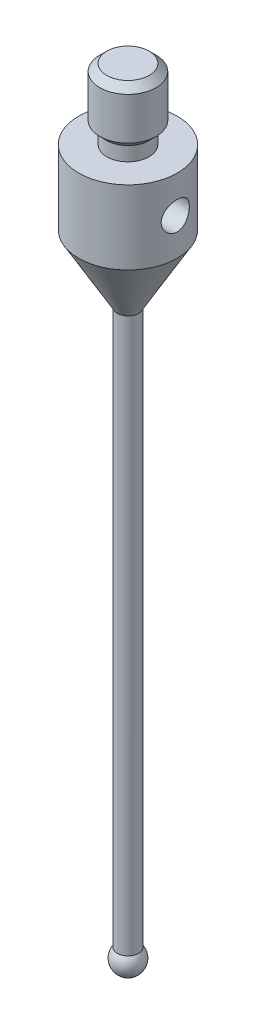
SolidWorks part; units mm, degrees
ref_plane "Front Plane" through (0, 0, 0) normal (0, 0, 1) x (1, 0, 0)
ref_plane "Top Plane" through (0, 0, 0) normal (0, 1, 0) x (1, 0, 0)
ref_plane "Right Plane" through (0, 0, 0) normal (1, 0, 0) x (0, 0, -1)
sketch "Sketch1" plane through (0, 0, 0) normal (0, 0, 1) x (1, 0, 0)
  line L0 (0, 0) -> (0, -1)
  line L1 (0, 0) -> (0, 1)
  arc A0 (0, 1) -> (0, -1) centre (0, 0) cw
  point P5 (0, -0.8177)
  dimension "D1" = 2
revolve "Revolve1" add sketch "Sketch1" angle 360 about L1 other way angle 360
sketch "Sketch2" plane through (0, 0, 0) normal (0, 1, 0) x (1, 0, 0)
  circle A0 centre (0, 0) radius 0.375
  circle A1 centre (0, 0) radius 0.75
  dimension "D1" = 0.75
  dimension "D2" = 1.5
extrude "Boss-Extrude2" add sketch "Sketch2" along normal blind 40 contours A1
sketch "Sketch4" plane through (0, 40, 0) normal (0, 1, 0) x (1, 0, 0)
  circle A0 centre (0, 0) radius 3.5
  dimension "D1" = 7
extrude "Boss-Extrude3" add sketch "Sketch4" along normal blind 10
chamfer "Chamfer1" distance 2.75 angle 60 1 edges at (0, 40, 3.5) first distance on face at (0, 40, 0.75)
sketch "Sketch5" plane through (0, 0, 0) normal (1, 0, 0) x (0, 0, -1)
  line L0 (0, 50) -> (0, 44.7631) construction
  line L1 (3.5, 50) -> (-3.5, 50) construction
  line L2 (-3.5, 44.7631) -> (3.5, 44.7631) construction
  circle A0 centre (0, 47.3816) radius 1
  point P2 (0, 47.3816)
  dimension "D1" = 2
extrude "Cut-Extrude4" cut sketch "Sketch5" against normal through all both and the other way through all
sketch "Sketch6" plane through (0, 50, 0) normal (0, 1, 0) x (1, 0, 0)
  circle A0 centre (0, 0) radius 1.5
  dimension "D1" = 3
extrude "Boss-Extrude4" add sketch "Sketch6" along normal blind 1
sketch "Sketch7" plane through (0, 51, 0) normal (0, 1, 0) x (1, 0, 0)
  circle A0 centre (0, 0) radius 2
  dimension "D1" = 4
extrude "Boss-Extrude5" add sketch "Sketch7" along normal blind 4
chamfer "Chamfer2" distance 0.5 angle 45 2 edges at (0, 55, 2) (0, 51, 2)
